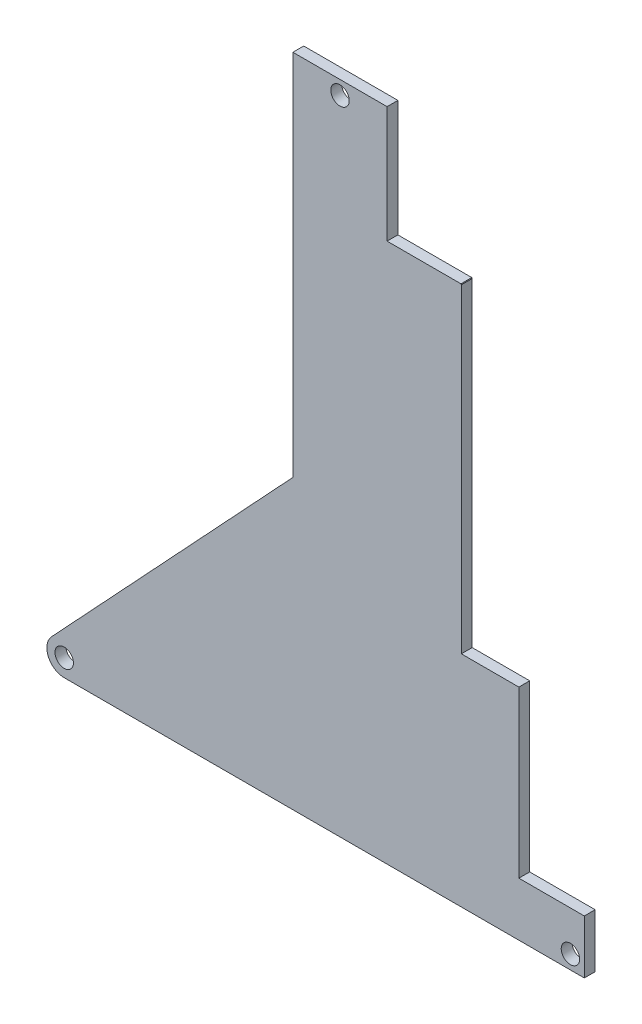
SolidWorks part; units mm, degrees
ref_plane "Front Plane" through (0, 0, 0) normal (0, 0, 1) x (1, 0, 0)
ref_plane "Top Plane" through (0, 0, 0) normal (0, 1, 0) x (1, 0, 0)
ref_plane "Right Plane" through (0, 0, 0) normal (1, 0, 0) x (0, 0, -1)
sketch "Sketch1" plane through (0, 0, 0) normal (0, 0, 1) x (1, 0, 0)
  line L1 (-52.6486, -67.2724) -> (-30.5784, -43.6209)
  line L2 (-62.4049, -73.074) -> (-22.4391, -30.2446) construction
  line L3 (-30.5784, -43.6209) -> (-18.8373, -31.0385)
  line L4 (-18.8373, 22.9178) -> (-18.8373, 15.0967)
  line L5 (-62.4049, -73.074) -> (-22.4391, -30.2446) construction
  line L6 (-54.2124, -68.9483) -> (-52.6486, -67.2724)
  line L7 (-60.0836, -75.2401) -> (-20.1178, -32.4107) construction
  line L9 (23.8665, -73.2212) -> (-30.5784, -73.2212)
  line L11 (-22.0123, -29.1615) -> (-22.0123, 29.2678) construction
  line L12 (-18.8373, 15.0967) -> (-18.8373, -31.0385)
  line L13 (-30.5784, -73.2212) -> (-52.3554, -73.2212)
  line L14 (-18.8373, 22.9178) -> (-5.0365, 22.9178)
  line L20 (23.8665, -65.3472) -> (23.8665, -73.2212)
  arc A0 (25.454, -65.3472) -> (-3.6178, 23.6674) centre (-125.3585, -65.3472) ccw construction
  arc A1 (25.454, -65.3472) -> (-3.6178, 23.6674) centre (-125.3585, -65.3472) ccw construction
  arc A2 (23.8665, -65.3472) -> (-5.0365, 22.9178) centre (-125.3585, -65.3472) ccw
  arc A3 (23.8665, -65.3472) -> (-4.8993, 22.7304) centre (-125.3585, -65.3472) ccw construction
  circle A6 centre (-16.8688, 16.5678) radius 2.4426 construction
  arc A7 (-52.3554, -73.2212) -> (-54.2124, -68.9483) centre (-52.3554, -70.6812) cw
  dimension "D4" = 6.35
  dimension "D5" = 2.54
  dimension "D1" = 1.5875
  dimension "D2" = 3.175
  dimension "D3" = 3.175
extrude "Boss-Extrude1" add sketch "Sketch1" along normal blind 1.5875
hole_wizard "#2 Clearance Hole1" positions "Sketch3" profile "Sketch2" hole size "#2" standard "ANSI Inch" end condition through all
sketch "Sketch3" plane through (0, 0, 0) normal (0, 0, -1) x (-1, 0, 0)
  line L0 (11.9369, 20.8858) -> (11.9369, 22.9178) construction
  line L1 (5.0365, 22.9178) -> (18.8373, 22.9178) construction
  line L2 (-23.8665, -73.2212) -> (-23.8665, -65.3472) construction
  line L3 (52.3554, -73.2212) -> (-23.8665, -73.2212) construction
  point P0 (-21.8345, -71.1892)
  point P2 (52.3554, -70.6812)
  point P5 (11.9369, 20.8858)
  dimension "D1" = 2.032
  dimension "D2" = 2.032
  dimension "D3" = 2.032
sketch "Sketch2" plane through (21.8345, -71.1892, 0) normal (1, 0, 0) x (0, 1, 0)
  line L0 (0, 0) -> (0, 1.5875)
  line L1 (0, 1.5875) -> (1.3525, 1.5875)
  line L2 (1.3525, 1.5875) -> (1.3525, 0)
  line L5 (1.3525, 0) -> (0, 0)
  line L11 (0, -6.35) -> (0, 107.95) construction
  dimension "Thru Hole Dia." = 2.7051
  dimension "Thru Hole Depth" = 1.5875
sketch "Sketch4" plane through (0, 0, 0) normal (0, 0, -1) x (-1, 0, 0)
  line L1 (-23.8665, -65.3472) -> (-14.278, -65.3472)
  line L2 (-23.8665, -65.3472) -> (-23.8665, -41.0902)
  line L3 (-23.8665, -41.0902) -> (-14.278, -41.0902)
  line L4 (-14.278, -65.3472) -> (-14.278, -41.0902)
  line L5 (-23.8665, -65.3472) -> (-14.278, -41.0902) construction
  line L6 (-23.8665, -41.0902) -> (-14.278, -65.3472) construction
  line L8 (-14.278, -41.0902) -> (-9.1472, -41.0902) construction
  line L9 (-14.278, -73.9832) -> (-14.278, -41.0902) construction
  line L10 (-5.8452, 5.8452) -> (-21.8817, 5.8452)
  line L11 (-5.8452, 5.8452) -> (-5.8452, -41.0902)
  line L12 (-5.8452, -41.0902) -> (-21.8817, -41.0902)
  line L13 (-21.8817, 5.8452) -> (-21.8817, -41.0902)
  line L14 (-5.8452, 5.8452) -> (-21.8817, -41.0902) construction
  line L15 (-5.8452, -41.0902) -> (-21.8817, 5.8452) construction
  line L16 (5.0365, 22.9178) -> (-5.8452, 22.9178)
  line L17 (5.0365, 22.9178) -> (5.0365, 5.8452)
  line L18 (5.0365, 5.8452) -> (-5.8452, 5.8452)
  line L19 (-5.8452, 22.9178) -> (-5.8452, 5.8452)
  line L20 (5.0365, 22.9178) -> (-5.8452, 5.8452) construction
  line L21 (5.0365, 5.8452) -> (-5.8452, 22.9178) construction
  arc A0 (5.0365, 22.9178) -> (-23.8665, -65.3472) centre (125.3585, -65.3472) ccw construction
  point P4 (-19.0722, -53.2187)
  point P14 (-13.8635, -17.6225)
  point P23 (-0.4043, 14.3815)
  arc M8 (5.0365, 22.9178) -> (-23.8665, -65.3472) centre (125.3585, -65.3472) ccw
extrude "Cut-Extrude1" cut sketch "Sketch4" against normal through all contours L1 L4 L3 M8 | L12 L11 L3 M8 | L18 L17 M8 region at (18.7619, -53.6674, 0) region at (11.7225, -24.2369, 0) region at (-1.3365, 11.675, 0)
